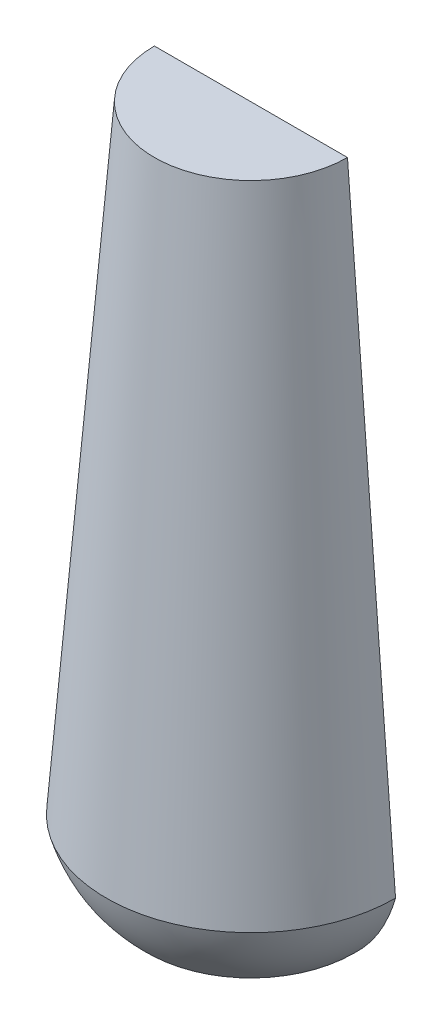
SolidWorks part; units mm, degrees
ref_plane "Front Plane" through (0, 0, 0) normal (0, 0, 1) x (1, 0, 0)
ref_plane "Top Plane" through (0, 0, 0) normal (0, 1, 0) x (1, 0, 0)
ref_plane "Right Plane" through (0, 0, 0) normal (1, 0, 0) x (0, 0, -1)
sketch "Sketch1" plane through (0, 0, 0) normal (0, 0, 1) x (1, 0, 0)
  line L0 (27.686, 0) -> (22.606, 0)
  line L1 (22.606, 0) -> (22.606, 1.8288)
  line L2 (28.829, 4.191) -> (22.606, 4.191)
  line L3 (22.606, 4.191) -> (22.606, 5.8928)
  line L4 (22.606, 5.8928) -> (30.607, 5.8928)
  line L5 (36.5429, 18.669) -> (0, 18.669)
  line L6 (0, 18.669) -> (0, 185.547)
  line L7 (0, 185.547) -> (26.0985, 185.547)
  line L8 (26.0985, 185.547) -> (39.0906, 18.669)
  line L9 (36.5429, 18.669) -> (35.5415, 31.5318) construction
  line L10 (27.686, 0) -> (-4.9317, -30.4165) construction
  line L11 (39.0906, 18.669) -> (57.9001, 81.973) construction
  line L12 (34.3825, 10.171) -> (26.8315, 1.6146) construction
  line L13 (30.8955, 5.835) -> (26.7625, 2.547) construction
  line L14 (22.606, 1.8288) -> (0, 1.8288) construction
  spline S0 degree 3 poles (27.686, 0) (33.0192, 4.9733) (36.7329, 10.7342) (39.0906, 18.669) knots 0 0 0 0 1 1 1 1
  spline S1 degree 3 poles (22.606, 1.8288) (25.0412, 1.8288) (27.1069, 2.821) (28.829, 4.191) knots 0 0 0 0 0.286843 0.286843 0.286843 0.286843
  spline S2 degree 2 poles (30.607, 5.8928) (35.3264, 11.2406) (36.5429, 18.669) knots 0.392904 0.392904 0.392904 1 1 1
  dimension "D1" = 185.547
  dimension "D2" = 39.0906
  dimension "D3" = 18.669
  dimension "D4" = 22.606
  dimension "D5" = 5.08
  dimension "D6" = 1.8288
  dimension "D7" = 2.3622
  dimension "D8" = 6.223
  dimension "D9" = 1.7018
  dimension "D10" = 8.001
  dimension "D11" = 26.0985
  dimension "D12" = 2.54
  dimension "D13" = 43
  dimension "D14" = 21
revolve "Revolve1" add sketch "Sketch1" angle 180 about L6 reverse direction yes
